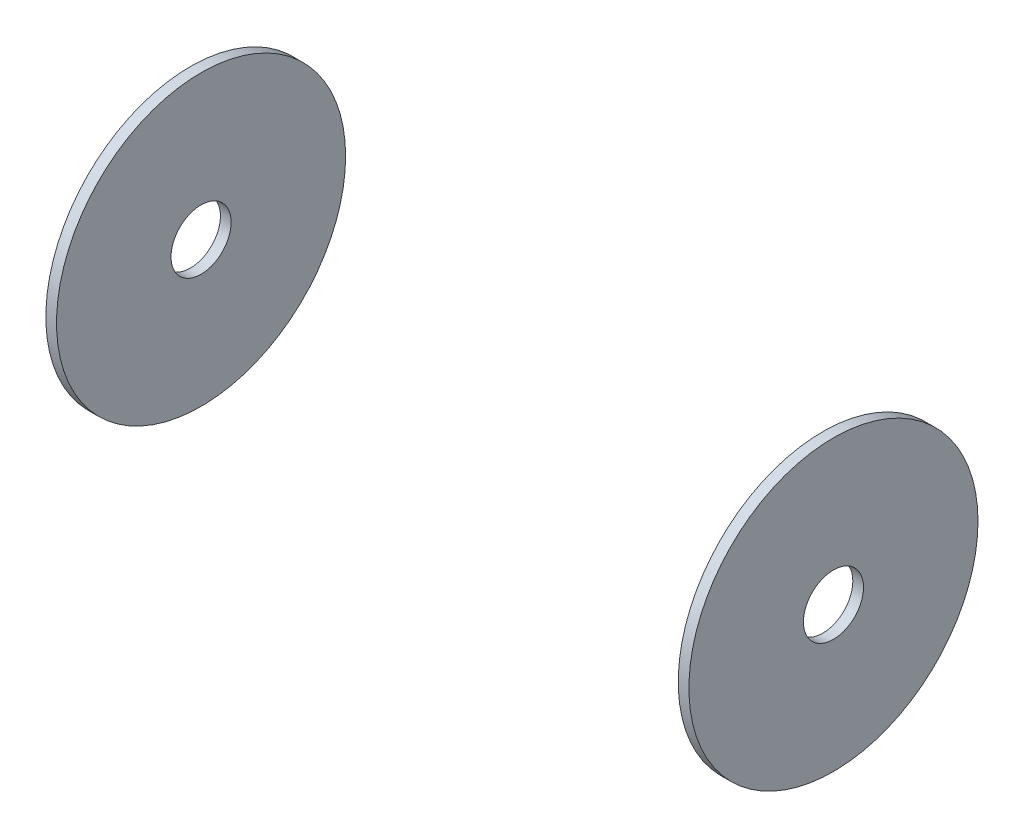
SolidWorks part; units mm, degrees
material "Titanium"
ref_plane "Front Plane" through (0, 0, 0) normal (0, 0, 1) x (1, 0, 0)
ref_plane "Top Plane" through (0, 0, 0) normal (0, 1, 0) x (1, 0, 0)
ref_plane "Right Plane" through (0, 0, 0) normal (1, 0, 0) x (0, 0, -1)
sketch "Sketch1" plane through (43.7, 0, 0) normal (1, 0, 0) x (0, 0, -1)
  circle A0 centre (-177.8, 26.67) radius 20.32
  arc A1 (-196.2562, 35.1713) -> (-195.2627, 16.2798) centre (-177.8, 26.67) ccw construction
  circle A2 centre (-177.8, 26.67) radius 4.2227
  dimension "D1" = 8.4455
extrude "Boss-Extrude1" add sketch "Sketch1" along normal blind 1.5
mirror "Mirror2" about plane through (0, 0, 0) normal (1, 0, 0) of bodies 101
equation "\"weapon shaft threads\"= 5 / 16"
equation "\"D1@Sketch1\"=\"weapon shaft threads\" + .02in"
equation "\"D1@Boss-Extrude1\"=1.5mm"
